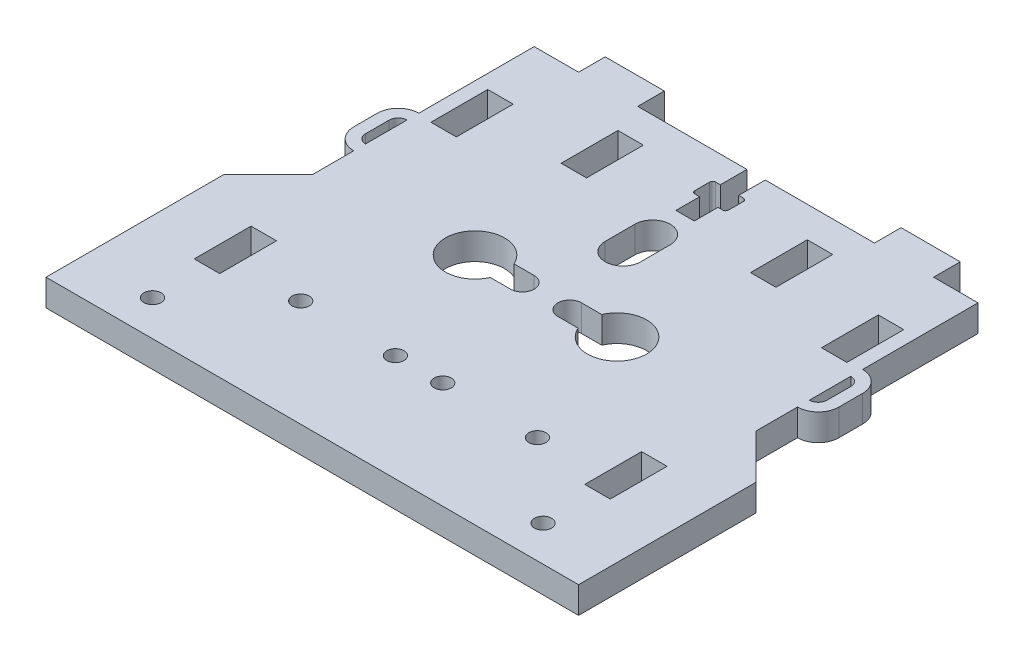
SolidWorks part; units mm, degrees
ref_plane "Front Plane" through (0, 0, 0) normal (0, 0, 1) x (1, 0, 0)
ref_plane "Top Plane" through (0, 0, 0) normal (0, 1, 0) x (1, 0, 0)
ref_plane "Right Plane" through (0, 0, 0) normal (1, 0, 0) x (0, 0, -1)
sketch "Sketch1" plane through (0, 0, 0) normal (0, 1, 0) x (1, 0, 0)
  line L1 (-37.5, 37.5) -> (37.5, 37.5)
  line L2 (-37.5, 37.5) -> (-37.5, -37.5)
  line L3 (-37.5, -37.5) -> (37.5, -37.5)
  line L4 (37.5, 37.5) -> (37.5, -37.5)
  line L5 (-37.5, 37.5) -> (37.5, -37.5) construction
  line L6 (-37.5, -37.5) -> (37.5, 37.5) construction
  point P0 (0, 0)
  dimension "D1" = 75
  dimension "D2" = 75
extrude "MainShape" add sketch "Sketch1" along normal blind 4.5
sketch "Sketch2" plane through (0, 4.5, 0) normal (0, 1, 0) x (1, 0, 0)
  line L0 (0, -37.5) -> (0, 37.5) construction
  line L1 (-37.5, -37.5) -> (37.5, -37.5) construction
  line L2 (37.5, 37.5) -> (-37.5, 37.5) construction
  line L4 (-5, 42) -> (5, 42)
  line L5 (-5, 42) -> (-5, 33)
  line L6 (-5, 33) -> (5, 33)
  line L7 (5, 42) -> (5, 33)
  line L8 (-5, 42) -> (5, 33) construction
  line L9 (-5, 33) -> (5, 42) construction
  dimension "D1" = 10
  dimension "D2" = 4.5
extrude "Tab1" [suppressed] add sketch "Sketch2" against normal through all
sketch "Sketch4" [suppressed] plane through (0, 4.5, 0) normal (0, 1, 0) x (1, 0, 0)
  line L0 (0, 42) -> (0, -37.5) construction
  line L1 (5, 42) -> (-5, 42) construction
  line L2 (-47.5, -37.5) -> (47.5, -37.5) construction
  line L3 (-40, 37.5) -> (-40, 27) construction
  line L4 (-5, 37.5) -> (-47.5, 37.5) construction
  line L5 (-38.25, 27) -> (-41.75, 27) construction
  line L6 (-41.75, 27) -> (-41.75, 37.5) construction
  line L7 (-38.25, 27) -> (-41.75, 27)
  line L8 (-41.75, 27) -> (-41.75, 29.5)
  line L9 (-41.75, 29.5) -> (-42.75, 29.5)
  line L10 (-43, 29.75) -> (-43, 33.45)
  line L11 (-42.75, 33.7) -> (-41.75, 33.7)
  line L12 (-41.75, 33.7) -> (-41.75, 37.5)
  line L13 (-41.75, 37.5) -> (-38.25, 37.5)
  line L14 (-38.25, 27) -> (-38.25, 37.5) construction
  line L15 (-38.25, 33.7) -> (-38.25, 37.5)
  line L16 (-37.25, 33.7) -> (-38.25, 33.7)
  line L17 (-37, 29.75) -> (-37, 33.45)
  line L18 (-38.25, 29.5) -> (-37.25, 29.5)
  line L19 (-38.25, 27) -> (-38.25, 29.5)
  line L20 (38.25, 27) -> (38.25, 37.5) construction
  line L21 (41.75, 27) -> (41.75, 37.5) construction
  line L22 (38.25, 27) -> (41.75, 27) construction
  line L23 (40, 37.5) -> (40, 27) construction
  line L24 (38.25, 27) -> (38.25, 29.5)
  line L25 (38.25, 29.5) -> (37.25, 29.5)
  line L26 (37, 29.75) -> (37, 33.45)
  line L27 (37.25, 33.7) -> (38.25, 33.7)
  line L28 (38.25, 33.7) -> (38.25, 37.5)
  line L29 (41.75, 37.5) -> (38.25, 37.5)
  line L30 (41.75, 33.7) -> (41.75, 37.5)
  line L31 (42.75, 33.7) -> (41.75, 33.7)
  line L32 (43, 29.75) -> (43, 33.45)
  line L33 (41.75, 29.5) -> (42.75, 29.5)
  line L34 (41.75, 27) -> (41.75, 29.5)
  line L35 (38.25, 27) -> (41.75, 27)
  arc A0 (-42.75, 29.5) -> (-43, 29.75) centre (-42.75, 29.75) cw
  arc A1 (-37, 29.75) -> (-37.25, 29.5) centre (-37.25, 29.75) cw
  arc A2 (-37.25, 33.7) -> (-37, 33.45) centre (-37.25, 33.45) cw
  arc A3 (-43, 33.45) -> (-42.75, 33.7) centre (-42.75, 33.45) cw
  arc A4 (43, 33.45) -> (42.75, 33.7) centre (42.75, 33.45) ccw
  arc A5 (37.25, 33.7) -> (37, 33.45) centre (37.25, 33.45) ccw
  arc A6 (37, 29.75) -> (37.25, 29.5) centre (37.25, 29.75) ccw
  arc A7 (42.75, 29.5) -> (43, 29.75) centre (42.75, 29.75) ccw
  point P24 (-43, 29.5)
  point P27 (-37, 29.5)
  point P30 (-37, 33.7)
  point P33 (-43, 33.7)
  point P56 (43, 33.7)
  point P57 (37, 33.7)
  point P58 (37, 29.5)
  point P59 (43, 29.5)
  dimension "D7" = 0.5
  dimension "D1" = 11
  dimension "D2" = 1.55
  dimension "D3" = 3.5
  dimension "D4" = 2.85
  dimension "D5" = 8
  dimension "D6" = 40
extrude "Cut-Extrude2" [suppressed] cut sketch "Sketch4" against normal through all
sketch "Sketch5" plane through (0, 4.5, 0) normal (0, 1, 0) x (1, 0, 0)
  line L0 (0, -37.5) -> (0, 37.5) construction
  line L1 (-37.5, -37.5) -> (37.5, -37.5) construction
  line L3 (33, 37.5) -> (33, -37.5) construction
  line L4 (37.5, 37.5) -> (-37.5, 37.5) construction
  line L5 (-33, 37.5) -> (-33, -37.5) construction
  line L6 (30.85, 27.3) -> (35.15, 27.3)
  line L7 (30.85, 27.3) -> (30.85, 17.7)
  line L8 (30.85, 17.7) -> (35.15, 17.7)
  line L9 (35.15, 27.3) -> (35.15, 17.7)
  line L10 (30.85, 27.3) -> (35.15, 17.7) construction
  line L11 (30.85, 17.7) -> (35.15, 27.3) construction
  line L12 (-30.85, 17.7) -> (-35.15, 27.3) construction
  line L13 (-30.85, 27.3) -> (-35.15, 17.7) construction
  line L14 (-35.15, 27.3) -> (-35.15, 17.7)
  line L15 (-30.85, 17.7) -> (-35.15, 17.7)
  line L16 (-30.85, 27.3) -> (-30.85, 17.7)
  line L17 (-30.85, 27.3) -> (-35.15, 27.3)
  line L18 (-37.5, 2.5) -> (37.5, 2.5) construction
  line L19 (-37.5, 37.5) -> (-37.5, -37.5) construction
  line L20 (37.5, -37.5) -> (37.5, 37.5) construction
  line L21 (-30.85, -22.3) -> (-35.15, -12.7) construction
  line L22 (-30.85, -12.7) -> (-35.15, -22.3) construction
  line L23 (30.85, -12.7) -> (35.15, -22.3) construction
  line L24 (30.85, -22.3) -> (35.15, -12.7) construction
  line L25 (-30.85, -22.3) -> (-35.15, -22.3)
  line L26 (-30.85, -22.3) -> (-30.85, -12.7)
  line L27 (-30.85, -12.7) -> (-35.15, -12.7)
  line L28 (-35.15, -22.3) -> (-35.15, -12.7)
  line L29 (35.15, -22.3) -> (35.15, -12.7)
  line L30 (30.85, -12.7) -> (35.15, -12.7)
  line L31 (30.85, -22.3) -> (30.85, -12.7)
  line L32 (30.85, -22.3) -> (35.15, -22.3)
  line L33 (-30.85, 27.3) -> (-35.15, 17.7) construction
  line L34 (-37.5, 37.5) -> (37.5, 37.5) construction
  line L35 (37.5, 37.5) -> (-37.5, 37.5) construction
  point P10 (33, 22.5)
  point P21 (-33, 22.5)
  point P36 (-33, -17.5)
  point P37 (33, -17.5)
  dimension "D1" = 33
  dimension "D2" = 9.6
  dimension "D3" = 4.3
  dimension "D4" = 15
  dimension "D5" = 40
extrude "Cut-Extrude3" cut sketch "Sketch5" against normal through all
sketch "Sketch6" plane through (0, 4.5, 0) normal (0, 1, 0) x (1, 0, 0)
  line L0 (-18, -37.5) -> (-18, 28) construction
  line L1 (-24, -15.5) -> (-24, -7.5208)
  line L3 (-37.5, -15.5) -> (37.5, -15.5) construction
  line L4 (-37.5, 37.5) -> (-37.5, -37.5) construction
  line L5 (37.5, -37.5) -> (37.5, 37.5) construction
  line L6 (37.5, 37.5) -> (-37.5, 37.5) construction
  line L7 (-37.5, -37.5) -> (37.5, -37.5) construction
  line L8 (-12, -15.5) -> (-12, -7.5208)
  line L9 (-37.5, 37.5) -> (37.5, 37.5) construction
  arc A0 (-24, -15.5) -> (-12, -15.5) centre (-18, -15.5) ccw
  arc A2 (-12, -7.5208) -> (-24, -7.5208) centre (-18, -1.5) ccw
  dimension "D1" = 12
  dimension "D6" = 8.5
  dimension "D2" = 53
  dimension "D3" = 0
  dimension "D5" = 0
  dimension "D7" = 14
  dimension "D4" = 18
extrude "Cut-Extrude4" [suppressed] cut sketch "Sketch6" against normal through all
sketch "Sketch13" plane through (0, 4.5, 0) normal (0, 1, 0) x (1, 0, 0)
  line L0 (-37.5, 0) -> (-45, -7.5)
  line L1 (-37.5, 37.5) -> (-37.5, -37.5) construction
  line L2 (-45, -7.5) -> (-45, -37.5)
  line L3 (-45, -37.5) -> (-37.5, -37.5)
  line L4 (-37.5, -37.5) -> (-37.5, 0)
  line L5 (0, 37.5) -> (0, -37.5) construction
  line L6 (37.5, 37.5) -> (-37.5, 37.5) construction
  line L7 (-37.5, -37.5) -> (37.5, -37.5) construction
  line L8 (37.5, -37.5) -> (37.5, 0)
  line L9 (45, -37.5) -> (37.5, -37.5)
  line L10 (45, -7.5) -> (45, -37.5)
  line L11 (37.5, 0) -> (45, -7.5)
  line L12 (-37.5, -37.5) -> (-37.5, 0)
  line M23 (37.5, -37.5) -> (37.5, 37.5)
  line M25 (-37.5, 37.5) -> (-37.5, -37.5)
  dimension "D1" = 45
  dimension "D2" = 30
extrude "Boss-Extrude2" add sketch "Sketch13" against normal through all contours L2 L3 L0 M25 | L11 L9 L10 M23 region at (-41.1111, 4.5, 20.5556) region at (41.1111, 4.5, 20.5556)
sketch "Sketch8" [suppressed] plane through (0, 4.5, 0) normal (0, 1, 0) x (1, 0, 0)
  line L0 (-18, -9.5) -> (-18, -21.5) construction
  line L1 (-18, -15.5) -> (-39.46, -15.5) construction
  line L2 (-39.46, -23.5) -> (-39.46, -7.5) construction
  line L3 (-18, -21.5) -> (-18, -9.5) construction
  circle A0 centre (-39.46, -7.5) radius 1.45
  circle A1 centre (-18, -15.5) radius 6 construction
  circle A2 centre (-39.46, -23.5) radius 1.45
  dimension "D3" = 2.9
  dimension "D1" = 0
  dimension "D2" = 8
  dimension "D4" = 21.46
extrude "Cut-Extrude6" [suppressed] cut sketch "Sketch8" against normal through all
mirror "Mirror1" [suppressed] about plane through (0, 0, 0) normal (1, 0, 0)
sketch "Sketch11" plane through (0, 4.5, 0) normal (0, 1, 0) x (1, 0, 0)
  line L0 (0, 37.5) -> (0, -37.5) construction
  line L1 (37.5, 37.5) -> (-37.5, 37.5) construction
  line L2 (-45, -37.5) -> (45, -37.5) construction
  line L3 (-25, 42) -> (-25, 37.5) construction
  line L4 (-30, 37.5) -> (-20, 37.5)
  line L5 (-30, 37.5) -> (-30, 42)
  line L6 (-30, 42) -> (-20, 42)
  line L7 (-20, 37.5) -> (-20, 42)
  line L8 (25, 42) -> (25, 37.5) construction
  line L9 (20, 37.5) -> (20, 42)
  line L10 (30, 42) -> (20, 42)
  line L11 (30, 37.5) -> (30, 42)
  line L12 (30, 37.5) -> (20, 37.5)
  dimension "D1" = 10
  dimension "D2" = 4.5
  dimension "D3" = 25
extrude "RearTabs" add sketch "Sketch11" against normal through all
sketch "Sketch12" plane through (0, 4.5, 0) normal (0, 1, 0) x (1, 0, 0)
  line L0 (0, 0) -> (0, 37.5) construction
  line L1 (20, 37.5) -> (-20, 37.5) construction
  line L2 (1.55, 37.5) -> (-1.55, 37.5)
  line L3 (-1.55, 37.5) -> (-1.55, 33)
  line L4 (-1.55, 33) -> (-2.35, 33)
  line L5 (-2.85, 32.5) -> (-2.85, 30)
  line L6 (-2.35, 29.5) -> (-1.55, 29.5)
  line L7 (-1.55, 29.5) -> (-1.55, 25.5)
  line L8 (-1.55, 25.5) -> (1.55, 25.5)
  line L9 (1.55, 29.5) -> (1.55, 25.5)
  line L10 (2.35, 29.5) -> (1.55, 29.5)
  line L11 (2.85, 32.5) -> (2.85, 30)
  line L12 (1.55, 33) -> (2.35, 33)
  line L13 (1.55, 37.5) -> (1.55, 33)
  arc A0 (-2.85, 30) -> (-2.35, 29.5) centre (-2.35, 30) ccw
  arc A1 (-2.35, 33) -> (-2.85, 32.5) centre (-2.35, 32.5) ccw
  arc A2 (2.35, 33) -> (2.85, 32.5) centre (2.35, 32.5) cw
  arc A3 (2.85, 30) -> (2.35, 29.5) centre (2.35, 30) cw
  point P14 (-2.85, 29.5)
  point P17 (-2.85, 33)
  point P25 (0, 25.5)
  point P28 (2.85, 33)
  point P29 (2.85, 29.5)
  dimension "D5" = 8
  dimension "D1" = 12
  dimension "D6" = 0.5
  dimension "D2" = 3.5
  dimension "D3" = 2.85
  dimension "D4" = 1.55
extrude "FrontScrewSlot" cut sketch "Sketch12" against normal through all
sketch "Sketch14" plane through (0, 4.5, 0) normal (0, 1, 0) x (1, 0, 0)
  line L0 (-33, 27.3) -> (-33, -37.5) construction
  line L1 (-30.85, 27.3) -> (-35.15, 27.3) construction
  line L2 (-45, -37.5) -> (45, -37.5) construction
  line L3 (-30, 37.5) -> (-37.5, 37.5) construction
  line L4 (0, 0) -> (0, -37.5) construction
  line L5 (33, 27.3) -> (33, -37.5) construction
  line L6 (-33, 27.3) -> (-33, -37.5) construction
  circle A0 centre (-33, -31.5) radius 1.45
  circle A1 centre (33, -31.5) radius 1.45
  dimension "D2" = 2.9
  dimension "D1" = 69
extrude "BraceScrews" cut sketch "Sketch14" against normal through all
sketch "Sketch15" plane through (0, 4.5, 0) normal (0, 1, 0) x (1, 0, 0)
  line L0 (0, -37.5) -> (0, 25.5) construction
  line L1 (-45, -37.5) -> (45, -37.5) construction
  line L2 (-1.55, 25.5) -> (1.55, 25.5) construction
  line L3 (16, 27.5) -> (-16, 27.5) construction
  line L4 (-1.55, 37.5) -> (-20, 37.5) construction
  line L5 (-18.15, 32.3) -> (-13.85, 32.3)
  line L6 (-18.15, 32.3) -> (-18.15, 22.7)
  line L7 (-18.15, 22.7) -> (-13.85, 22.7)
  line L8 (-13.85, 32.3) -> (-13.85, 22.7)
  line L9 (-18.15, 32.3) -> (-13.85, 22.7) construction
  line L10 (-18.15, 22.7) -> (-13.85, 32.3) construction
  line L11 (18.15, 22.7) -> (13.85, 32.3) construction
  line L12 (18.15, 32.3) -> (13.85, 22.7) construction
  line L13 (13.85, 32.3) -> (13.85, 22.7)
  line L14 (18.15, 22.7) -> (13.85, 22.7)
  line L15 (18.15, 32.3) -> (18.15, 22.7)
  line L16 (18.15, 32.3) -> (13.85, 32.3)
  point P19 (0, 27.5)
  dimension "D1" = 16
  dimension "D2" = 4.3
  dimension "D3" = 9.6
  dimension "D4" = 10
extrude "FanTabs" cut sketch "Sketch15" against normal through all
sketch "Sketch16" plane through (0, 4.5, 0) normal (0, 1, 0) x (1, 0, 0)
  line L0 (0, 0) -> (0, 25.5) construction
  line L1 (-1.55, 25.5) -> (1.55, 25.5) construction
  line L2 (0, 20) -> (0, 15) construction
  line L3 (3, 20) -> (3, 15)
  line L4 (-3, 20) -> (-3, 15)
  arc A0 (3, 20) -> (-3, 20) centre (0, 20) ccw
  arc A1 (-3, 15) -> (3, 15) centre (0, 15) ccw
  point P7 (0, 17.5)
  dimension "D1" = 3
  dimension "D2" = 20
  dimension "D3" = 5
extrude "WiringSlot" cut sketch "Sketch16" against normal through all
sketch "Sketch17" plane through (0, 4.5, 0) normal (0, 1, 0) x (1, 0, 0)
  line L0 (-37.5, 14.5) -> (-37.5, 10.5) construction
  line L3 (-37.5, 37.5) -> (-37.5, 0) construction
  line L4 (-36, 14.5) -> (-36, 10.5)
  line L5 (-39, 14.5) -> (-39, 10.5)
  line L6 (-37.5, 14.5) -> (-37.5, 10.5) construction
  line L7 (-34, 14.5) -> (-34, 10.5)
  line L8 (-41, 14.5) -> (-41, 10.5)
  line L9 (-41, 12.5) -> (-37.5, 12.5) construction
  line L10 (0, 0) -> (0, -12.1805) construction
  arc A0 (-36, 14.5) -> (-39, 14.5) centre (-37.5, 14.5) ccw
  arc A1 (-39, 10.5) -> (-36, 10.5) centre (-37.5, 10.5) ccw
  arc A2 (-34, 14.5) -> (-41, 14.5) centre (-37.5, 14.5) ccw
  arc A3 (-41, 10.5) -> (-34, 10.5) centre (-37.5, 10.5) ccw
  point P4 (-37.5, 12.5)
  point P10 (-37.5, 12.5)
  dimension "D4" = 4
  dimension "D5" = 25
  dimension "D1" = 0
  dimension "D2" = 2
  dimension "D3" = 1.5
extrude "Boss-Extrude3" add sketch "Sketch17" against normal through all
mirror "Mirror2" about plane through (0, 0, 0) normal (1, 0, 0) of "Boss-Extrude3"
sketch "Sketch18" plane through (0, 4.5, 0) normal (0, 1, 0) x (1, 0, 0)
  line L0 (0, -37.5) -> (0, 47.6111) construction
  line L1 (-45, -37.5) -> (45, -37.5) construction
  line L2 (-12, 2) -> (-12, -19.46) construction
  line L3 (-4, -19.46) -> (-20, -19.46) construction
  circle A0 centre (-12, 2) radius 5
  circle A1 centre (-20, -19.46) radius 1.45
  circle A2 centre (-4, -19.46) radius 1.45
  dimension "D2" = 8
  dimension "D4" = 21.46
  dimension "D1" = 2.9
  dimension "D3" = 10
  dimension "D5" = 12
  dimension "D6" = 2
extrude "Cut-Extrude7" cut sketch "Sketch18" against normal through all
mirror "Mirror3" about plane through (0, 0, 0) normal (1, 0, 0) of "Cut-Extrude7"
sketch "Sketch19" plane through (0, 4.5, 0) normal (0, 1, 0) x (1, 0, 0)
  line L0 (-17, 2) -> (-7, 2) construction
  line L1 (-12, 2) -> (-4, 2) construction
  line L2 (-12, 4) -> (-4, 4)
  line L3 (-12, 0) -> (-4, 0)
  line L4 (-12, 7) -> (-12, -3) construction
  line L5 (0, 0) -> (0, 6.8806) construction
  line L6 (12, 7) -> (12, -3) construction
  line L7 (17, 2) -> (7, 2) construction
  line L8 (12, 2) -> (4, 2) construction
  line L9 (12, 4) -> (4, 4)
  line L10 (12, 0) -> (4, 0)
  circle A0 centre (-12, 2) radius 5 construction
  arc A1 (-12, 4) -> (-12, 0) centre (-12, 2) ccw
  arc A2 (-4, 0) -> (-4, 4) centre (-4, 2) ccw
  arc A3 (12, 4) -> (12, 0) centre (12, 2) cw
  arc A4 (4, 0) -> (4, 4) centre (4, 2) cw
  point P6 (-8, 2)
  point P23 (8, 2)
  dimension "D1" = 2
  dimension "D2" = 8
extrude "Cut-Extrude8" cut sketch "Sketch19" against normal through all
equation "\"X-ROD-SPACING\"=45"
equation "\"Y-ROD-SPACING\"=75"
equation "\"Z-ROD-SPACING\"=17.5"
equation "\"Y-BED-OFFSET\"=2"
equation "\"Y-BED-ROD-INSET\"=3.5"
equation "\"Y-BED-SCREW-SPACING\"=209"
equation "\"Y-BED-SCREW-CUTOUT-SLOT-HEIGHT\"=2"
equation "\"T-SLOT-NUT-FILLET-RADIUS\"=0.5"
equation "\"T-SLOT-SCREW-SHAFT-RADIUS\"=1.55"
equation "\"T-SLOT-SCREW-SHAFT-CUTOUT-LENGTH\"=11.0"
equation "\"T-SLOT-NUT-DEPTH\"=3.5"
equation "\"T-SLOT-NUT-WIDTH\"=2.85"
equation "\"T-SLOT-NUT-END-DISTANCE\"=8"
equation "\"ACRYLIC-THICKNESS\"=10"
equation "\"ACRYLIC-THICKNESS2\"=4.5"
equation "\"ACRYLIC-TAB-CUTOUT-SIZE\"=\"ACRYLIC-THICKNESS\"+\"ACRYLIC-TAB-TOLERANCE\"*2"
equation "\"ACRYLIC-TAB-WIDTH\"=\"ACRYLIC-THICKNESS\""
equation "\"ACRYLIC-M3-HOLE\"=2.9"
equation "\"SMOOTHROD-CAP-SCREW-DISTANCE\"=20"
equation "\"FRAME-WIDTH-INNER\"=370"
equation "\"NEMA17-HOLE-SPACING\"=31"
equation "\"NEMA17-CENTRAL-CUTOUT\"=22.5"
equation "\"Z-BRACKET-REACH\"=55"
equation "\"Z-ROD-INSET\"=16"
equation "\"TOP-BRACKET-SPACING\"=40"
equation "\"SMOOTHROD-X-LENGTH\"=350"
equation "\"SMOOTHROD-Y-LENGTH\"=350"
equation "\"SMOOTHROD-Z-LENGTH\"=350"
equation "\"SMOOTHROD-TIGHTENING-HEADROOM\"=.25"
equation "\"LEADSCREW-Z-LENGTH\"=300"
equation "\"SCREW-LENGTH-FRAME\"=\"ACRYLIC-THICKNESS\" + 10"
equation "\"SCREW-LENGTH-MOTOR\"=\"ACRYLIC-THICKNESS\" + 5"
equation "\"SCREW-LENGTH-EXTRUDER\"=28"
equation "\"SCREW-HEAD-RADIUS\"=6"
equation "\"PRINTED-X-SMOOTHROD-DIAMETER\"=9.0"
equation "\"PRINTED-X-SMOOTHROD-CUTOUT\"=10"
equation "\"PRINTED-X-BASE-HEIGHT\"=10"
equation "\"PRINTED-LM8UU-CUTOUT-SIZE\"=15.5"
equation "\"PRINTED-LM8UU-CUTOUT-LENGTH\"=24.5"
equation "\"PRINTED-X-IDLER-HEIGHT\"=16"
equation "\"PSU-MOUNTING-WIDTH\"=95"
equation "\"PSU-MOUNTING-HEIGHT\"=177"
equation "\"Y-BELT-TO-ROD-DISTANCE\"=20"
equation "\"SPOOL-HOLDER-ROD-SPACING\"=150"
equation "\"ACRYLIC-X-CARRIAGE-WIDTH\"=55"
equation "\"ACRYLIC-X-CARRIAGE-HEIGHT\"=75"
equation "\"ACRYLIC-X-CARRIAGE-SCREW-SPACING-X\"=15"
equation "\"ACRYLIC-X-CARRIAGE-SCREW-SPACING-Y\"=33"
equation "\"ACRYLIC-X-CARRIAGE-CENTER-TAB-SPACING\"=14"
equation "\"D1@MainShape\" = \"ACRYLIC-THICKNESS2\""
equation "\"D1@Sketch2\"=\"ACRYLIC-TAB-WIDTH\""
equation "\"D2@Sketch2\"=\"ACRYLIC-THICKNESS2\""
equation "\"D1@Sketch4\"=\"T-SLOT-SCREW-SHAFT-CUTOUT-LENGTH\""
equation "\"D2@Sketch4\"=\"T-SLOT-SCREW-SHAFT-RADIUS\""
equation "\"D3@Sketch4\"=\"T-SLOT-NUT-DEPTH\""
equation "\"D4@Sketch4\"=\"T-SLOT-NUT-WIDTH\""
equation "\"D5@Sketch4\"=\"T-SLOT-NUT-END-DISTANCE\""
equation "\"D7@Sketch4\"=\"T-SLOT-NUT-FILLET-RADIUS\""
equation "\"ACRYLIC-X-CARRIAGE-EXTRUDER-SHELF-DEPTH\"=\"ACRYLIC-X-CARRIAGE-EXTRUDER-OFFSET\" + 28"
equation "\"ACRYLIC-X-CARRIAGE-LM8UU-CUTOUT-WIDTH\"=24.25"
equation "\"ACRYLIC-X-CARRIAGE-EXTRUDER-BRACE-SPACING\"=23"
equation "\"ACRYLIC-X-CARRIAGE-EXTRUDER-BRACE-TAB-OFFSET\"=20"
equation "\"ACRYLIC-X-CARRIAGE-EXTRUDER-BRACE-HEIGHT\"=35"
equation "\"ACRYLIC-X-CARRIAGE-EXTRUDER-BRACE-SCREW-SPACING\"=22"
equation "\"D2@Sketch5\"=\"ACRYLIC-THICKNESS2-TAB-CUTOUT-HEIGHT\""
equation "\"D3@Sketch5\"=\"ACRYLIC-THICKNESS2-TAB-CUTOUT-WIDTH\""
equation "\"D3@Sketch8\"=\"ACRYLIC-M3-HOLE\""
equation "\"ACRYLIC-X-CARRIAGE-EXTRUDER-ANGLE\"=90"
equation "\"ACRYLIC-X-CARRIAGE-EXTRUDER-OFFSET\"=26"
equation "\"ACRYLIC-TAB-TOLERANCE\"=-.05"
equation "\"ACRYLIC-X-CARRIAGE-DUAL-WIDTH-MULTIPLIER\"=1.65"
equation "\"ACRYLIC-X-CARRIAGE-DUAL-HOTEND-SPACING\"=42"
equation "\"ACRYLIC-X-CARRIAGE-DUAL-WIDTH\"=75"
equation "\"ACRYLIC-X-CARRIAGE-DUAL-HOTEND-SEPARATION\"=36"
equation "\"ACRYLIC-X-CARRIAGE-DUAL-MOUNT-PLATE-DEPTH\"=75"
equation "\"ACRYLIC-X-CARRIAGE-DUAL-MOUNT-BRACE-WIDTH\"=33"
equation "\"D1@Sketch5\"=\"ACRYLIC-X-CARRIAGE-DUAL-MOUNT-BRACE-WIDTH\""
equation "\"ACRYLIC-X-CARRIAGE-DUAL-MOUNT-SCREW-WIDTH\"=40"
equation "\"D6@Sketch4\"=\"ACRYLIC-X-CARRIAGE-DUAL-MOUNT-SCREW-WIDTH\""
equation "\"D1@Sketch1\"=\"ACRYLIC-X-CARRIAGE-DUAL-WIDTH\""
equation "\"D2@Sketch1\"=\"ACRYLIC-X-CARRIAGE-DUAL-MOUNT-PLATE-DEPTH\""
equation "\"D4@Sketch6\"=\"ACRYLIC-X-CARRIAGE-DUAL-HOTEND-SEPARATION\"/2"
equation "\"D1@Sketch11\"=\"ACRYLIC-TAB-WIDTH\""
equation "\"D2@Sketch11\"=\"ACRYLIC-THICKNESS2\""
equation "\"D1@Sketch12\"=\"T-SLOT-SCREW-SHAFT-CUTOUT-LENGTH\"+1"
equation "\"D2@Sketch12\"=\"T-SLOT-NUT-DEPTH\""
equation "\"D3@Sketch12\"=\"T-SLOT-NUT-WIDTH\""
equation "\"D4@Sketch12\"=\"T-SLOT-SCREW-SHAFT-RADIUS\""
equation "\"D5@Sketch12\"=\"T-SLOT-NUT-END-DISTANCE\""
equation "\"D6@Sketch12\"=\"T-SLOT-NUT-FILLET-RADIUS\""
equation "\"D2@Sketch14\"=\"ACRYLIC-M3-HOLE\""
equation "\"D2@Sketch15\"=\"ACRYLIC-THICKNESS2-TAB-CUTOUT-WIDTH\""
equation "\"D3@Sketch15\"=\"ACRYLIC-THICKNESS2-TAB-CUTOUT-HEIGHT\""
equation "\"KERF\"=0.1"
equation "\"PRINTED-M3-HOLE\"=3.5"
equation "\"PRINTED-M3-NUT-AF\"=6.25"
equation "\"ACRYLIC-X-CARRIAGE-LM8UU-CUTOUT-HEIGHT\"=11.0"
equation "\"ACRYLIC-X-CARRIAGE-DUAL-FAN-OFFSET\"=52"
equation "\"ACRYLIC-X-CARRIAGE-DUAL-FAN-HEIGHT\"=20"
equation "\"BLOWER-FAN-WIDTH\"=15"
equation "\"ACRYLIC-THICKNESS-TAB-CUTOUT-WIDTH\"=\"ACRYLIC-THICKNESS\"-\"KERF\"*2"
equation "\"ACRYLIC-THICKNESS-TAB-CUTOUT-HEIGHT\"=\"ACRYLIC-TAB-WIDTH\"-\"KERF\"*4"
equation "\"ACRYLIC-THICKNESS2-TAB-CUTOUT-WIDTH\"=\"ACRYLIC-THICKNESS2\"-\"KERF\"*2"
equation "\"ACRYLIC-THICKNESS2-TAB-CUTOUT-HEIGHT\"=\"ACRYLIC-TAB-WIDTH\"-\"KERF\"*4"
equation "\"D1@Sketch18\"=\"ACRYLIC-M3-HOLE\""
